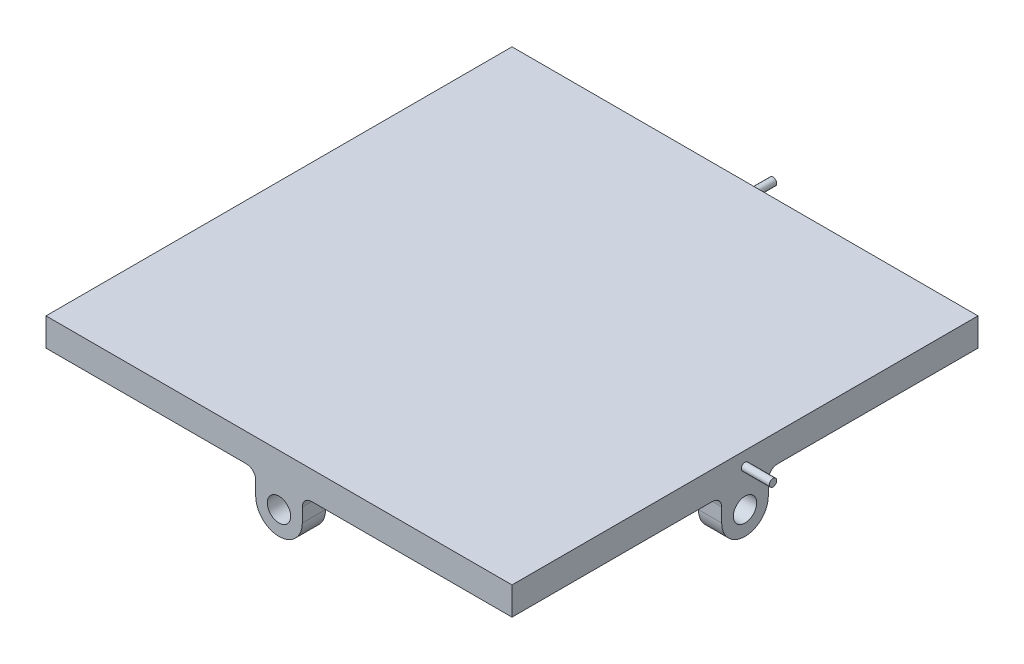
SolidWorks part; units mm, degrees
ref_plane "Plano frontal" through (0, 0, 0) normal (0, 0, 1) x (1, 0, 0)
ref_plane "Plano superior" through (0, 0, 0) normal (0, 1, 0) x (1, 0, 0)
ref_plane "Plano direito" through (0, 0, 0) normal (1, 0, 0) x (0, 0, -1)
sketch "Esboço1" plane through (0, 0, 0) normal (0, 1, 0) x (1, 0, 0)
  line L1 (0, 0) -> (500, 0)
  line L2 (0, 0) -> (0, 500)
  line L3 (0, 500) -> (500, 500)
  line L4 (500, 0) -> (500, 500)
  dimension "D1" = 500
extrude "Ressalto-extrusão1" add sketch "Esboço1" along normal blind 30
sketch "Esboço2" plane through (0, 0, 0) normal (0, -1, 0) x (1, 0, 0)
  line L0 (0, -500) -> (0, 0) construction
  line L1 (225, -25) -> (275, -25)
  line L2 (225, -25) -> (225, 0)
  line L3 (225, 0) -> (275, 0)
  line L4 (275, -25) -> (275, 0)
  line L5 (0, 0) -> (500, 0) construction
  line L6 (500, 0) -> (500, -500) construction
  line L7 (475, -225) -> (500, -225)
  line L9 (500, -500) -> (0, -500) construction
  line L14 (475, -225) -> (475, -275)
  line L15 (475, -275) -> (500, -275)
  line L16 (500, -225) -> (500, -275)
  line L22 (0, -225) -> (0, -275)
  line L23 (25, -275) -> (0, -275)
  line L24 (25, -225) -> (25, -275)
  line L25 (25, -225) -> (0, -225)
  line L26 (275, -475) -> (275, -500)
  line L27 (225, -500) -> (275, -500)
  line L28 (225, -475) -> (225, -500)
  line L29 (225, -475) -> (275, -475)
  point P6 (250, 0)
  point P21 (500, -250)
  dimension "D1" = 250
  dimension "D2" = 50
  dimension "D3" = 25
  dimension "D4" = 0
  dimension "D5" = 250
  dimension "D6" = 50
  dimension "D7" = 25
  dimension "D8" = 0
extrude "Ressalto-extrusão2" add sketch "Esboço2" along normal blind 50
sketch "Esboço3" plane through (0, 0, 0) normal (-1, 0, 0) x (0, 0, 1)
  line L3 (-225, -50) -> (-275, -50) construction
  line L4 (-275, -50) -> (-275, 0) construction
  circle A0 centre (-250, -25) radius 12.5
  dimension "D3" = 25
  dimension "D1" = 25
  dimension "D2" = 25
extrude "Corte-extrusão1" cut sketch "Esboço3" against normal through all
sketch "Esboço4" plane through (0, 0, 0) normal (0, 0, 1) x (1, 0, 0)
  line L0 (275, -50) -> (275, 0) construction
  line L1 (0, 0) -> (225, 0) construction
  circle A0 centre (250, -25) radius 12.5
  dimension "D3" = 25
  dimension "D1" = 25
  dimension "D2" = 25
extrude "Corte-extrusão2" cut sketch "Esboço4" against normal through all
fillet "Filete1" radius 25 8 edges at (275, -50, -487.5) (225, -50, -487.5) (12.5, -50, -275) (12.5, -50, -225) (487.5, -50, -275) (487.5, -50, -225) (275, -50, -12.5) (225, -50, -12.5)
fillet "Filete4" radius 10 8 edges at (487.5, 0, -275) (487.5, 0, -225) (275, 0, -12.5) (225, 0, -12.5) (12.5, 0, -225) (275, 0, -487.5) (225, 0, -487.5) (12.5, 0, -275)
sketch "Esboço5" plane through (0, 0, 0) normal (0, -1, 0) x (1, 0, 0)
  line L0 (25, -285) -> (25, -215) construction
  line L1 (50, -25) -> (450, -25)
  line L2 (25, -50) -> (25, -450)
  line L3 (50, -475) -> (450, -475)
  line L4 (475, -50) -> (475, -450)
  line L6 (215, -25) -> (285, -25) construction
  line L7 (475, -215) -> (475, -285) construction
  line L8 (285, -475) -> (215, -475) construction
  line L9 (25, -450) -> (50, -475)
  line L10 (450, -475) -> (475, -450)
  line L11 (25, -50) -> (50, -25)
  line L12 (450, -25) -> (475, -50)
  point P0 (25, -25)
  point P1 (475, -475)
  point P2 (25, -475)
  point P3 (475, -25)
extrude "Corte-extrusão3" cut sketch "Esboço5" against normal blind 15
sketch "Esboço6" plane through (500, 0, 0) normal (1, 0, 0) x (0, 0, -1)
  line L0 (250, 30) -> (250, -50) construction
  line L1 (0, 15) -> (500, 15) construction
  line L3 (0, 30) -> (500, 30) construction
  line L4 (0, 30) -> (0, 0) construction
  line L5 (500, 30) -> (500, 0) construction
  circle A0 centre (250, 15) radius 4
  dimension "D1" = 8
extrude "Ressalto-extrusão3" add sketch "Esboço6" along normal blind 30
sketch "Esboço7" plane through (0, 0, -500) normal (0, 0, -1) x (-1, 0, 0)
  line L0 (-250, 30) -> (-250, -50) construction
  line L1 (-500, 30) -> (0, 30) construction
  line L2 (-500, 15) -> (0, 15) construction
  line L3 (-500, 30) -> (-500, 0) construction
  line L4 (0, 30) -> (0, 0) construction
  circle A0 centre (-250, 15) radius 4
  dimension "D1" = 8
extrude "Ressalto-extrusão4" add sketch "Esboço7" along normal blind 30
sketch "Esboço8" plane through (0, 15, 0) normal (0, -1, 0) x (1, 0, 0)
  line L0 (0, -250) -> (500, -250) construction
  line L1 (500, -254) -> (500, -246) construction
  line L2 (250, 0) -> (250, -500) construction
  line L3 (246, -500) -> (254, -500) construction
  line L5 (234, -234) -> (266, -234)
  line L6 (234, -234) -> (234, -266)
  line L7 (234, -266) -> (266, -266)
  line L8 (266, -234) -> (266, -266)
  dimension "D1" = 32
  dimension "D2" = 32
  dimension "D3" = 16
  dimension "D4" = 16
extrude "Ressalto-extrusão5" add sketch "Esboço8" along normal blind 40
sketch "Esboço9" plane through (0, -25, 0) normal (0, -1, 0) x (1, 0, 0)
  line L0 (250, -234) -> (250, -266) construction
  line L1 (266, -234) -> (234, -234) construction
  line L2 (234, -266) -> (266, -266) construction
  line L3 (234, -250) -> (266, -250) construction
  line L4 (234, -234) -> (234, -266) construction
  line L5 (266, -266) -> (266, -234) construction
  line L7 (242.6, -242.6) -> (257.4, -242.6)
  line L8 (242.6, -242.6) -> (242.6, -257.4)
  line L9 (242.6, -257.4) -> (257.4, -257.4)
  line L10 (257.4, -242.6) -> (257.4, -257.4)
  dimension "D1" = 14.8
  dimension "D2" = 14.8
  dimension "D3" = 7.4
  dimension "D4" = 7.4
extrude "Corte-extrusão4" cut sketch "Esboço9" against normal blind 18
sketch "Esboço10" plane through (0, -25, 0) normal (0, -1, 0) x (1, 0, 0)
  line L0 (234, -250) -> (266, -250) construction
  line L1 (234, -234) -> (234, -266) construction
  line L2 (266, -266) -> (266, -234) construction
  line L3 (250, -234) -> (250, -266) construction
  line L4 (266, -234) -> (234, -234) construction
  line L5 (234, -266) -> (266, -266) construction
  circle A0 centre (250, -250) radius 7.9
  dimension "D1" = 15.8
extrude "Corte-extrusão5" cut sketch "Esboço10" against normal up to surface (18 mm away) up to face at (250, -7, -250)
